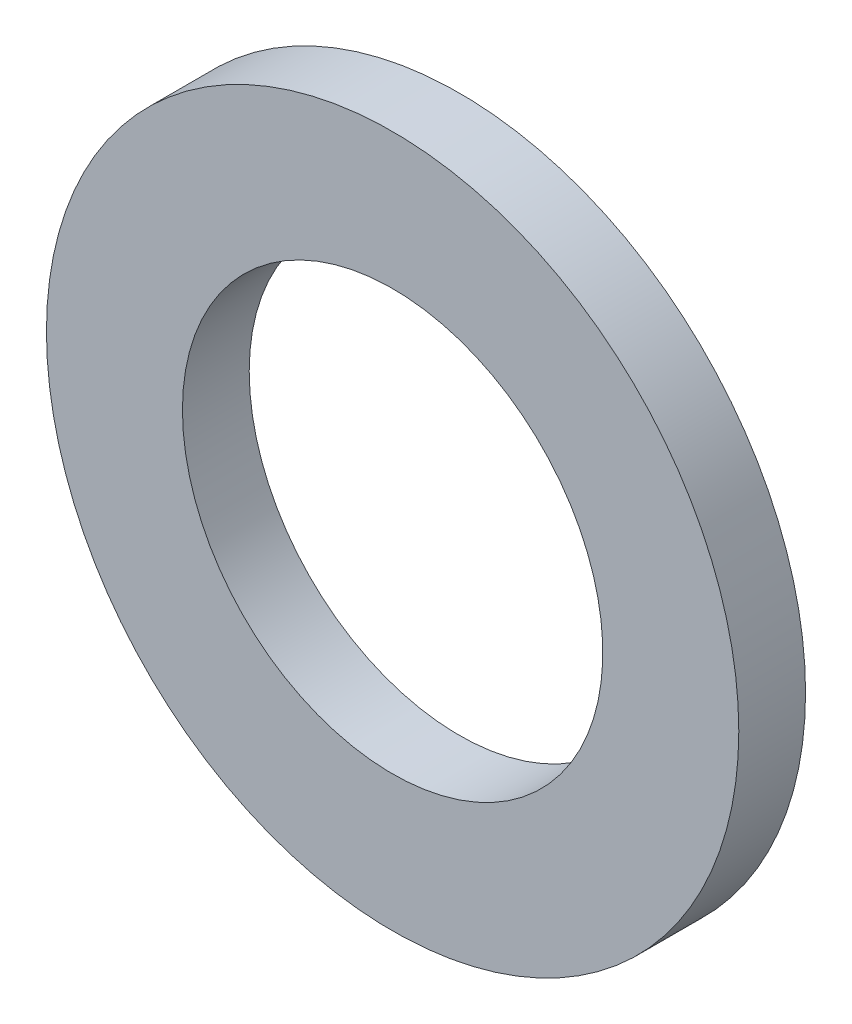
SolidWorks part; units mm, degrees
ref_plane "Front Plane" through (0, 0, 0) normal (0, 0, 1) x (1, 0, 0)
ref_plane "Top Plane" through (0, 0, 0) normal (0, 1, 0) x (1, 0, 0)
ref_plane "Right Plane" through (0, 0, 0) normal (1, 0, 0) x (0, 0, -1)
sketch "Sketch1" plane through (0, 0, 0) normal (0, 0, 1) x (1, 0, 0)
  circle A0 centre (0, 0) radius 14
  circle A1 centre (0, 0) radius 8.5
  dimension "OD" = 28
  dimension "ID1" = 17
extrude "Boss-Extrude1" add sketch "Sketch1" along normal blind 2.7
ref_axis "Center Axis 1" through (0, 0, 2.7) along (0, 0, -1)
ref_plane "Contact Plane 1" through (0, 0, 2.7) normal (0, 0, 1) x (1, 0, 0)
ref_plane "Contact Plane 2" through (0, 0, 0) normal (0, 0, -1) x (-1, 0, 0)
